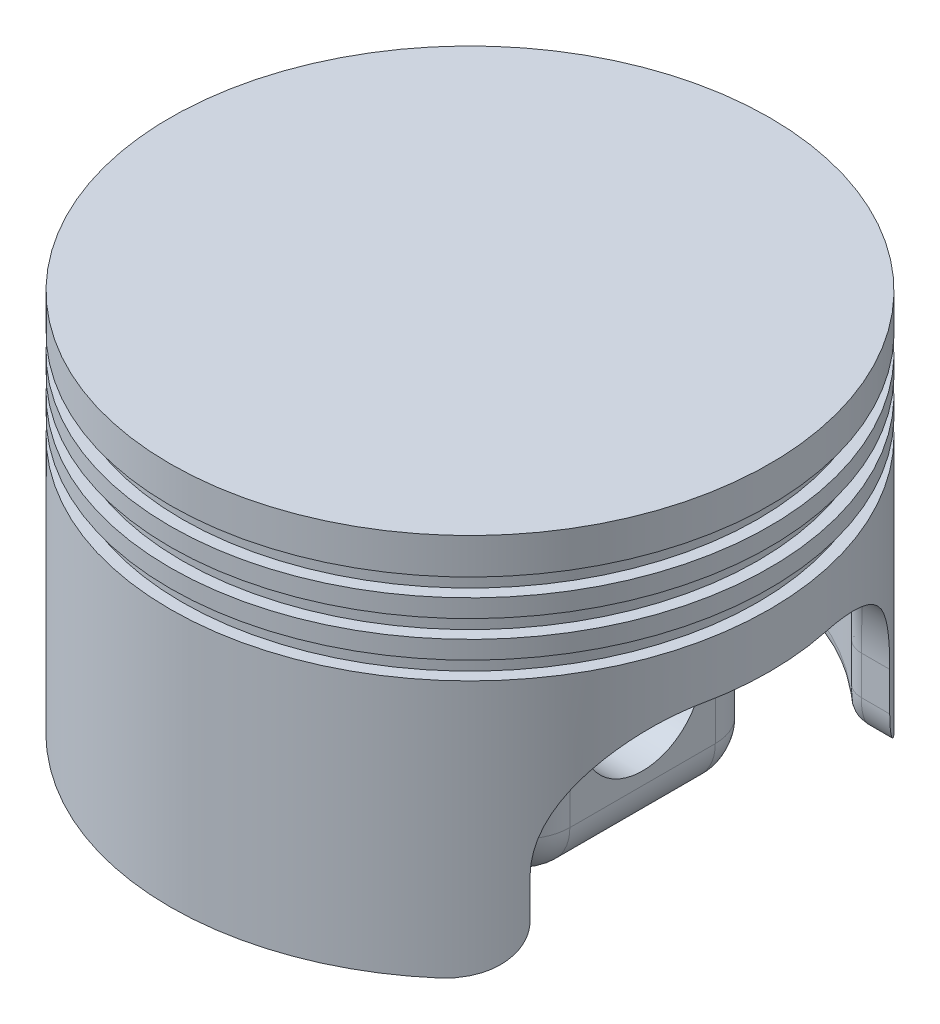
SolidWorks part; units mm, degrees
material "1060 Alloy"
ref_plane "Front Plane" through (0, 0, 0) normal (0, 0, 1) x (1, 0, 0)
ref_plane "Top Plane" through (0, 0, 0) normal (0, 1, 0) x (1, 0, 0)
ref_plane "Right Plane" through (0, 0, 0) normal (1, 0, 0) x (0, 0, -1)
sketch "Sketch1" plane through (0, 0, 0) normal (0, 0, 1) x (1, 0, 0)
  line L0 (0, 0) -> (63.5, 0)
  line L1 (63.5, 0) -> (63.5, -81.28)
  line L2 (63.5, -81.28) -> (57.15, -81.28)
  line L3 (57.15, -81.28) -> (57.15, -19)
  line L4 (57.15, -19) -> (0, -19)
  line L5 (0, -19) -> (0, 0)
  dimension "D1" = 63.5
  dimension "D2" = 81.28
  dimension "D3" = 6.35
  dimension "D4" = 19
revolve "Revolve1" add sketch "Sketch1" angle 360 about L5
sketch "Sketch2" plane through (0, 0, 0) normal (0, 0, 1) x (1, 0, 0)
  line L0 (63.5, -7.62) -> (60.96, -7.62)
  line L1 (60.96, -7.62) -> (60.96, -11.43)
  line L2 (60.96, -11.43) -> (63.5, -11.43)
  line L3 (63.5, -11.43) -> (63.5, -7.62)
  line L4 (63.5, 0) -> (-63.5, 0) construction
  dimension "D1" = 7.62
  dimension "D2" = 3.81
  dimension "D3" = 2.54
  dimension "D4" = 63.5
ref_axis "Axis1" through (0, 0, 0) along (0, -1, 0)
revolve "Cut-Revolve1" cut sketch "Sketch2" angle 360 about axis through (0, 0, 0) along (0, -1, 0)
pattern_linear "LPattern1" count 3 spacing 7.62 along (0, -1, 0) of "Cut-Revolve1"
sketch "Sketch3" plane through (0, 0, 0) normal (1, 0, 0) x (0, 0, -1)
  line L0 (0, 0) -> (0, -81.28) construction
  line L1 (-38.1, -81.28) -> (38.1, -81.28)
  line L2 (-38.1, -81.28) -> (-38.1, -38.1)
  line L3 (-38.1, -38.1) -> (38.1, -38.1)
  line L4 (38.1, -81.28) -> (38.1, -38.1)
  line L5 (-38.1, -81.28) -> (38.1, -38.1) construction
  line L6 (-38.1, -38.1) -> (38.1, -81.28) construction
  line L7 (-57.15, -81.28) -> (57.15, -81.28) construction
  point P0 (0, -59.69)
  dimension "D1" = 76.2
  dimension "D2" = 38.1
extrude "Cut-Extrude1" cut sketch "Sketch3" against normal mid plane 220
fillet "Fillet1" radius 25 4 edges at (-46.6985, -38.1, -38.1) (-46.6985, -38.1, 38.1) (46.6985, -38.1, 38.1) (46.6985, -38.1, -38.1)
fillet "Fillet2" radius 10 4 edges at (46.6985, -81.28, 38.1) (46.6985, -81.28, -38.1) (-46.6985, -81.28, -38.1) (-46.6985, -81.28, 38.1)
sketch "Sketch4" plane through (0, -19, 0) normal (0, -1, 0) x (1, 0, 0)
  line L1 (-36.55, -25.4) -> (-17.55, -25.4)
  line L2 (-36.55, -25.4) -> (-36.55, 25.4)
  line L3 (-36.55, 25.4) -> (-17.55, 25.4)
  line L4 (-17.55, -25.4) -> (-17.55, 25.4)
  line L5 (-36.55, -25.4) -> (-17.55, 25.4) construction
  line L6 (-36.55, 25.4) -> (-17.55, -25.4) construction
  point P0 (-27.05, 0)
  dimension "D1" = 19
  dimension "D2" = 50.8
  dimension "D3" = 17.55
extrude "Boss-Extrude1" add sketch "Sketch4" along normal blind 63.5
mirror "Mirror1" about plane through (0, 0, 0) normal (1, 0, 0) of "Boss-Extrude1"
fillet "Fillet3" radius 10 4 edges at (27.05, -82.5, -25.4) (27.05, -82.5, 25.4) (-27.05, -82.5, 25.4) (-27.05, -82.5, -25.4)
fillet "Fillet5" radius 10 10 edges at (36.55, -45.75, 25.4) (36.55, -79.5711, 22.4711) (36.55, -45.75, -25.4) (36.55, -79.5711, -22.4711) (36.55, -82.5, 0) (-17.55, -45.75, -25.4) (-17.55, -79.5711, -22.4711) (-17.55, -45.75, 25.4) (-17.55, -79.5711, 22.4711) (-17.55, -82.5, 0)
fillet "Fillet6" radius 10 10 edges at (-36.55, -45.75, 25.4) (-36.55, -79.5711, 22.4711) (-36.55, -45.75, -25.4) (-36.55, -79.5711, -22.4711) (-36.55, -82.5, 0) (17.55, -45.75, -25.4) (17.55, -79.5711, -22.4711) (17.55, -45.75, 25.4) (17.55, -79.5711, 22.4711) (17.55, -82.5, 0)
fillet "Fillet7" radius 5 1 edges at (0, -19, -57.15)
fillet "Fillet8" radius 5 16 edges at (41.3657, -76.2692, 39.4335) (42.5971, -67.19, 38.1) (49.5699, -43.3611, 28.4419) (57.15, -38.1, 0) (45.69, -49.8982, -34.33) (42.5971, -67.19, -38.1) (40.0022, -78.1316, -40.816) (0, -81.28, -57.15) (-41.3657, -76.2692, -39.4335) (-42.5971, -67.19, -38.1) (-49.5699, -43.3611, -28.4419) (-57.15, -38.1, 0) (-45.69, -49.8982, 34.33) (-42.5971, -67.19, 38.1) (-40.0022, -78.1316, 40.816) (0, -81.28, 57.15)
sketch "Sketch5" plane through (36.55, 0, 0) normal (1, 0, 0) x (0, 0, -1)
  line L0 (15.4, -82.5) -> (-15.4, -82.5) construction
  circle A0 centre (0, -57.1) radius 12.7
  dimension "D1" = 25.4
  dimension "D2" = 25.4
extrude "Cut-Extrude2" cut sketch "Sketch5" against normal through all both and the other way through all
